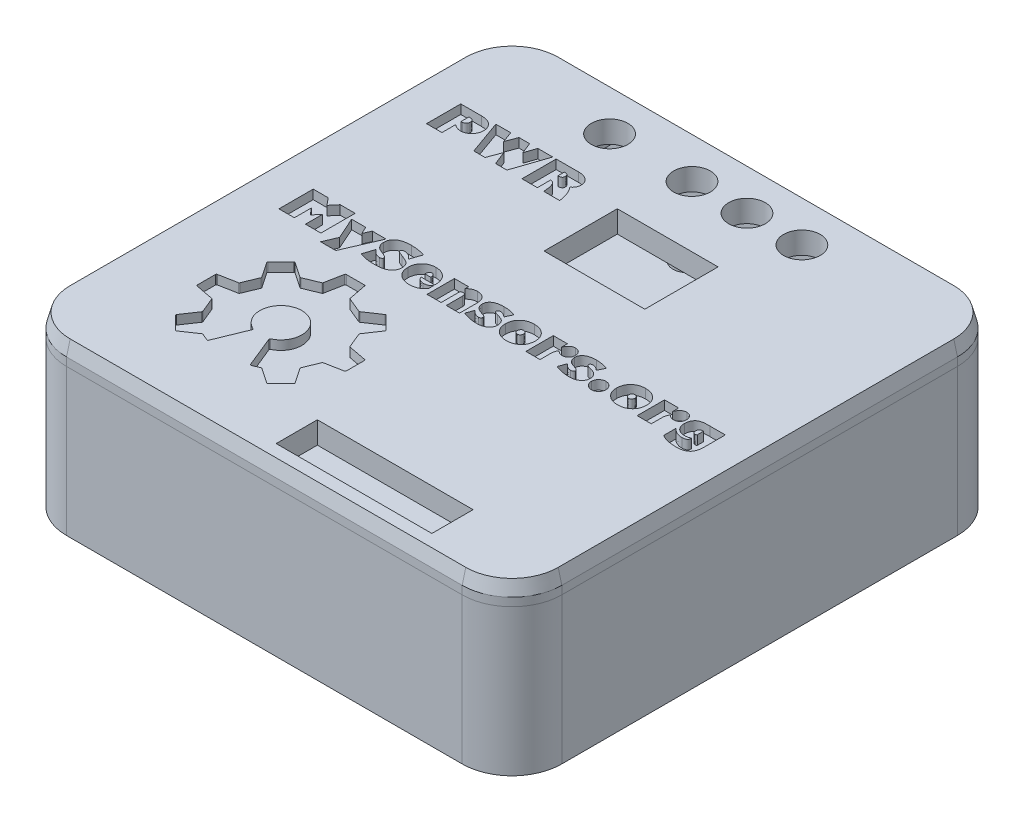
SolidWorks part; units mm, degrees
other "PCB"
other "Base"
other "Lid"
ref_plane "Front Plane" through (0, 0, 0) normal (0, 0, 1) x (1, 0, 0)
ref_plane "Top Plane" through (0, 0, 0) normal (0, 1, 0) x (1, 0, 0)
ref_plane "Right Plane" through (0, 0, 0) normal (1, 0, 0) x (0, 0, -1)
sketch "Sketch1" plane through (0, 0, 0) normal (0, 1, 0) x (1, 0, 0)
  line L1 (21.6, 25.6) -> (-21.6, 25.6)
  line L2 (25.6, 21.6) -> (25.6, -21.6)
  line L3 (21.6, -25.6) -> (-21.6, -25.6)
  line L4 (-25.6, 21.6) -> (-25.6, -21.6)
  line L5 (25.6, 25.6) -> (-25.6, -25.6) construction
  line L6 (25.6, -25.6) -> (-25.6, 25.6) construction
  line L10 (-27.04, 21.6) -> (-27.04, -21.6)
  line L11 (21.6, -27.04) -> (-21.6, -27.04)
  line L12 (27.04, 21.6) -> (27.04, -21.6)
  line L13 (21.6, 27.04) -> (-21.6, 27.04)
  circle A0 centre (-21, 21) radius 1.2
  circle A1 centre (-21, -21) radius 1.2
  circle A2 centre (21, 21) radius 1.2
  circle A3 centre (21, -21) radius 1.2
  arc A4 (-21.6, 25.6) -> (-25.6, 21.6) centre (-21.6, 21.6) ccw
  arc A5 (-21.6, -25.6) -> (-25.6, -21.6) centre (-21.6, -21.6) cw
  arc A6 (25.6, -21.6) -> (21.6, -25.6) centre (21.6, -21.6) cw
  arc A7 (21.6, 25.6) -> (25.6, 21.6) centre (21.6, 21.6) cw
  circle A8 centre (-21, 21) radius 2.2
  circle A9 centre (21, 21) radius 2.2
  circle A10 centre (21, -21) radius 1.6
  circle A11 centre (-21, -21) radius 2.2
  arc A12 (-21.6, -27.04) -> (-27.04, -21.6) centre (-21.6, -21.6) cw
  arc A13 (27.04, -21.6) -> (21.6, -27.04) centre (21.6, -21.6) cw
  arc A14 (21.6, 27.04) -> (27.04, 21.6) centre (21.6, 21.6) cw
  arc A15 (-21.6, 27.04) -> (-27.04, 21.6) centre (-21.6, 21.6) ccw
  point P0 (0, 0)
  dimension "D4" = 2.4
  dimension "D7" = 42
  dimension "D9" = 2.4
  dimension "D10" = 2.4
  dimension "D11" = 2.4
  dimension "D14" = 4
  dimension "D15" = 4
  dimension "D1" = 51.2
  dimension "D2" = 51.2
  dimension "D5" = 42
  dimension "D6" = 42
  dimension "D8" = 42
  dimension "D3" = 1
  dimension "D16" = 1.44
  dimension "D17" = 0.4
extrude "Boss-Extrude3" add sketch "Sketch1" along normal blind 13.99 contours L13 A15 L10 A12 L11 A13 L12 A14 L1 A7 L2 A6 L3 A5 L4 A4 region at (-24.9059, 0, -24.9059)
extrude "Boss-Extrude4" add sketch "Sketch1<3>" against normal blind 2 contours A7 L1 A4 L4 A5 L3 A6 L2 A11 A10 A9 A8 | L13 A15 L10 A12 L11 A13 L12 A14 L1 A7 L2 A6 L3 A5 L4 A4 | A11 A1 | A1 | A10 A3 | A3 | A8 A0 | A0 | A9 A2 | A2 region at (0.0589, 0, 0.0589) region at (-24.9059, 0, -24.9059) region at (-21, 0, -21) region at (-21, 0, 21) region at (21, 0, -21) region at (21, 0, 21) region at (-23.1378, 0, -21) region at (18.8622, 0, -21) region at (19.4453, 0, 21) region at (-23.1378, 0, 21)
sketch "Sketch1<3>" plane through (0, 0, 0) normal (0, 1, 0) x (1, 0, 0) same geometry as "Sketch1"
extrude "Boss-Extrude5" add sketch "Sketch1<4>" along normal blind 12.99 contours A3 | A1 | A2 | A0 region at (-21, 0, -21) region at (-21, 0, 21) region at (21, 0, -21) region at (21, 0, 21)
sketch "Sketch1<4>" plane through (0, 0, 0) normal (0, 1, 0) x (1, 0, 0) same geometry as "Sketch1"
extrude "Boss-Extrude6" add sketch "Sketch1<5>" along normal blind 7 contours A11 A1 | A8 A0 | A10 A3 | A9 A2 region at (-23.1378, 0, -21) region at (18.8622, 0, -21) region at (19.4453, 0, 21) region at (-23.1378, 0, 21)
sketch "Sketch1<5>" plane through (0, 0, 0) normal (0, 1, 0) x (1, 0, 0) same geometry as "Sketch1"
sketch "Sketch4" plane through (0, 7, 0) normal (0, 1, 0) x (1, 0, 0)
  line L1 (-21, 25) -> (21, 25)
  line L2 (-25, 21) -> (-25, -21)
  line L3 (-21, -25) -> (21, -25)
  line L4 (25, 21) -> (25, -21)
  line L5 (-25, 25) -> (25, -25) construction
  line L6 (-25, -25) -> (25, 25) construction
  arc A0 (-25, -21) -> (-21, -25) centre (-21, -21) ccw
  arc A1 (21, -25) -> (25, -21) centre (21, -21) ccw
  arc A2 (21, 25) -> (25, 21) centre (21, 21) cw
  arc A3 (-21, 25) -> (-25, 21) centre (-21, 21) ccw
  circle A4 centre (-21, 21) radius 1.4
  circle A5 centre (21, 21) radius 1.4
  circle A6 centre (21, -21) radius 1.4
  circle A7 centre (-21, -21) radius 1.4
  point P0 (0, 0)
  dimension "D3" = 4
  dimension "D4" = 2.8
  dimension "D5" = 2.8
  dimension "D6" = 2.8
  dimension "D7" = 2.8
  dimension "D1" = 50
  dimension "D2" = 50
  dimension "D8" = 4
  dimension "D9" = 4
  dimension "D10" = 4
  dimension "D11" = 4
extrude "Boss-Extrude7" add sketch "Sketch4" along normal blind 1.6 separate body
sketch "Sketch5" plane through (0, 8.6, 0) normal (0, 1, 0) x (1, 0, 0)
  line L0 (-21, -25) -> (21, -25) construction
  line L1 (-25, -9.2) -> (-19.2, -9.2)
  line L2 (-25, -9.2) -> (-25, -16.8)
  line L3 (-25, -16.8) -> (-19.2, -16.8)
  line L4 (-19.2, -9.2) -> (-19.2, -16.8)
  line L5 (-25, -9.2) -> (-19.2, -16.8) construction
  line L6 (-25, -16.8) -> (-19.2, -9.2) construction
  line L7 (-25, 3.8) -> (-19.2, 3.8)
  line L8 (-25, 3.8) -> (-25, -3.8)
  line L9 (-25, -3.8) -> (-19.2, -3.8)
  line L10 (-19.2, 3.8) -> (-19.2, -3.8)
  line L11 (-25, 3.8) -> (-19.2, -3.8) construction
  line L12 (-25, -3.8) -> (-19.2, 3.8) construction
  line L13 (-25, 21) -> (-25, -21) construction
  point P0 (-22.1, -13)
  point P5 (-22.1, 0)
  dimension "D4" = 7.6
  dimension "D5" = 5.8
  dimension "D6" = 5.8
  dimension "D7" = 7.6
  dimension "D8" = 12
  dimension "D9" = 25
extrude "Boss-Extrude8" add sketch "Sketch5" along normal blind 2.8
sketch "Sketch6" plane through (0, 8.6, 0) normal (0, 1, 0) x (1, 0, 0)
  line L0 (-25, 21) -> (-25, 3.8) construction
  line L1 (-21, -25) -> (21, -25) construction
  circle A0 centre (-12.0645, 22.1935) radius 1.55
  circle A1 centre (-3.0645, 22.1935) radius 1.55
  circle A2 centre (2.9355, 22.1935) radius 1.55
  circle A3 centre (8.9355, 22.1935) radius 1.55
  dimension "D1" = 3.1
  dimension "D2" = 12.9355
  dimension "D8" = 33.9355
  dimension "D3" = 47.1935
  dimension "D4" = 21.9355
  dimension "D5" = 47.1935
  dimension "D6" = 27.9355
  dimension "D7" = 47.1935
  dimension "D9" = 47.1935
extrude "Boss-Extrude9" add sketch "Sketch6" along normal blind 5
sketch "Sketch11" plane through (-27.04, 0, 0) normal (-1, 0, 0) x (0, 0, 1)
  line L0 (27.04, 13.99) -> (27.04, -2) construction
  line L4 (13, 11.4) -> (13, 8.6) construction
  line L6 (18.967, 6) -> (-8.033, 6)
  line L7 (18.967, 6) -> (18.967, 14)
  line L8 (18.967, 14) -> (-8.033, 14)
  line L9 (-8.033, 6) -> (-8.033, 14)
  line L11 (18.967, 6) -> (-8.033, 14) construction
  line L12 (0, 11.4) -> (0, 8.6) construction
  line L13 (-3.8, 10) -> (14.734, 10) construction
  line L14 (18.967, 14) -> (-8.033, 6) construction
  point P0 (0, 10)
  point P2 (5.467, 10)
  point P6 (13, 10)
  point P14 (5.467, 10)
  dimension "D1" = 27
  dimension "D2" = 8.073
  dimension "D3" = 8
extrude "Cut-Extrude1" cut sketch "Sketch11" against normal up to surface (1.44 mm away) up to face at (-25.6, 6.995, 0)
sketch "Sketch13" plane through (0, 13.99, 0) normal (0, 1, 0) x (1, 0, 0)
  line L0 (21.6, -27.04) -> (-21.6, -27.04) construction
  line L1 (27.04, 21.6) -> (27.04, -21.6) construction
  line L2 (21.6, 27.04) -> (-21.6, 27.04) construction
  line L4 (21.6, -27.04) -> (-21.6, -27.04)
  line L5 (27.04, 21.6) -> (27.04, -21.6)
  line L6 (21.6, 27.04) -> (-21.6, 27.04)
  line L7 (-27.04, -21.6) -> (-27.04, 21.6)
  arc A0 (-27.04, -21.6) -> (-21.6, -27.04) centre (-21.6, -21.6) ccw construction
  arc A1 (21.6, -27.04) -> (27.04, -21.6) centre (21.6, -21.6) ccw construction
  arc A2 (27.04, 21.6) -> (21.6, 27.04) centre (21.6, 21.6) ccw construction
  arc A3 (-21.6, 27.04) -> (-27.04, 21.6) centre (-21.6, 21.6) ccw construction
  arc A4 (-27.04, -21.6) -> (-21.6, -27.04) centre (-21.6, -21.6) ccw
  arc A5 (21.6, -27.04) -> (27.04, -21.6) centre (21.6, -21.6) ccw
  arc A6 (27.04, 21.6) -> (21.6, 27.04) centre (21.6, 21.6) ccw
  arc A7 (-21.6, 27.04) -> (-27.04, 21.6) centre (-21.6, 21.6) ccw
  circle A16 centre (-11.54, 22.1935) radius 2
  circle A17 centre (-2.54, 22.1935) radius 2
  circle A18 centre (3.46, 22.1935) radius 2
  circle A19 centre (9.46, 22.1935) radius 2
  dimension "D1" = 4
  dimension "D2" = 4
  dimension "D3" = 4
  dimension "D4" = 4
  dimension "D5" = 15.5
  dimension "D6" = 9
  dimension "D7" = 6
  dimension "D8" = 6
extrude "Boss-Extrude11" add sketch "Sketch13" along normal blind 2.4 separate body
chamfer "Chamfer1" distance 1.5 distance2 0.4 8 edges at (25.4467, 16.39, 25.4467) (27.04, 16.39, 0) (0, 16.39, 27.04) (25.4467, 16.39, -25.4467) (-25.4467, 16.39, 25.4467) (0, 16.39, -27.04) (-27.04, 16.39, 0) (-25.4467, 16.39, -25.4467) first distance on face at (24.8833, 15.19, 24.8833) first distance on face at (27.04, 15.19, 0) first distance on face at (0, 15.19, 27.04) first distance on face at (24.8833, 15.19, -24.8833) first distance on face at (-24.8833, 15.19, 24.8833) first distance on face at (0, 15.19, -27.04) first distance on face at (-27.04, 15.19, 0) first distance on face at (-24.8833, 15.19, -24.8833)
sketch "Sketch16" plane through (0, 13.99, 0) normal (0, -1, 0) x (1, 0, 0)
  circle A0 centre (21, 21) radius 1.4 construction
  circle A1 centre (21, 21) radius 1.4
  circle A2 centre (-21, 21) radius 1.4 construction
  circle A3 centre (-21, 21) radius 1.4
  circle A4 centre (21, -21) radius 1.4 construction
  circle A5 centre (21, -21) radius 1.4
  circle A6 centre (-21, -21) radius 1.4 construction
  circle A7 centre (-21, -21) radius 1.4
  circle A8 centre (-21, -21) radius 2.2 construction
  circle A9 centre (21, -21) radius 2.2 construction
  circle A11 centre (-21, 21) radius 2.2 construction
  circle A12 centre (-21, -21) radius 2.2
  circle A13 centre (21, -21) radius 2.2
  circle A14 centre (21, 21) radius 2.38
  circle A15 centre (-21, 21) radius 2.2
  dimension "D1" = 0.98
extrude "Boss-Extrude14" add sketch "Sketch16" along normal blind 2
sketch "Sketch17" plane through (0, 13.99, 0) normal (0, -1, 0) x (1, 0, 0)
  line L0 (-21.6, 23.6) -> (21.6, 23.6)
  line L1 (23.6, -21.6) -> (23.6, 21.6)
  line L2 (-21.6, 25.6) -> (21.6, 25.6)
  line L3 (-21.6, 25.6) -> (21.6, 25.6)
  line L4 (-21.6, -23.6) -> (-14.8497, -23.6)
  line L5 (-23.6, 21.6) -> (-23.6, 18.967)
  line L6 (-23.6, 18.967) -> (-24.1, 18.967)
  line L7 (-23.6, -21.6) -> (-25.6, -21.6)
  line L8 (12.271, -23.6) -> (12.271, -25.6)
  line L9 (-14.8497, -23.6) -> (-14.8497, -25.6)
  line L10 (12.271, -23.6) -> (21.6, -23.6)
  line L11 (12.271, -25.6) -> (21.6, -25.6)
  line L12 (-21.6, -23.6) -> (21.6, -23.6) construction
  line L14 (-21.6, -25.6) -> (21.6, -25.6) construction
  line L18 (-25.6, 21.6) -> (-25.6, -21.6)
  line L19 (-21.6, -25.6) -> (21.6, -25.6)
  line L20 (25.6, -21.6) -> (25.6, 21.6)
  line L21 (-25.6, 21.6) -> (-25.6, 18.967)
  line L22 (-21.6, -25.6) -> (-14.8497, -25.6)
  line L23 (25.6, -21.6) -> (25.6, 21.6)
  line L26 (-25.6, 18.967) -> (-24.1, 18.967)
  arc A0 (-21.6, 23.6) -> (-23.6, 21.6) centre (-21.6, 21.6) ccw
  arc A1 (23.6, 21.6) -> (21.6, 23.6) centre (21.6, 21.6) ccw
  arc A2 (21.6, -23.6) -> (23.6, -21.6) centre (21.6, -21.6) ccw
  arc A3 (-23.6, -21.6) -> (-21.6, -23.6) centre (-21.6, -21.6) ccw
  arc A20 (-21.6, 25.6) -> (-25.6, 21.6) centre (-21.6, 21.6) ccw
  arc A21 (-25.6, -21.6) -> (-21.6, -25.6) centre (-21.6, -21.6) ccw
  arc A22 (21.6, -25.6) -> (25.6, -21.6) centre (21.6, -21.6) ccw
  arc A23 (25.6, 21.6) -> (21.6, 25.6) centre (21.6, 21.6) ccw
  arc A24 (-21.6, 25.6) -> (-25.6, 21.6) centre (-21.6, 21.6) ccw
  arc A25 (-25.6, -21.6) -> (-21.6, -25.6) centre (-21.6, -21.6) ccw
  arc A26 (21.6, -25.6) -> (25.6, -21.6) centre (21.6, -21.6) ccw
  arc A27 (25.6, 21.6) -> (21.6, 25.6) centre (21.6, 21.6) ccw
  point P11 (-24.1, -21.1)
  point P12 (-24.1, 21.1)
  dimension "D1" = 1.44
  dimension "D2" = 1.44
  dimension "D4" = 2
extrude "Boss-Extrude15" add sketch "Sketch17" along normal blind 2
chamfer "Chamfer2" distance 1 distance2 0.2 7 edges at (24.4284, 11.99, -24.4284) (25.6, 11.99, 0) (24.4284, 11.99, 24.4284) (0, 11.99, 25.6) (-24.4284, 11.99, 24.4284) (-25.6, 11.99, 20.2835) (16.9355, 11.99, -25.6) first distance on face at (24.0142, 12.99, -24.0142) first distance on face at (25.6, 12.99, 0) first distance on face at (24.0142, 12.99, 24.0142) first distance on face at (0, 12.99, 25.6) first distance on face at (-24.0142, 12.99, 24.0142) first distance on face at (-25.6, 12.99, 20.2835) first distance on face at (16.9355, 12.99, -25.6)
chamfer "Chamfer3" distance 0.2 distance2 0.5 3 edges at (21, 11.99, -22.4) (-21, 11.99, -22.4) (-21, 11.99, 19.6) first distance on face at (21, 11.99, -23.2) first distance on face at (-21, 11.99, -23.2) first distance on face at (-21, 11.99, 18.8)
sketch "Sketch19" plane through (0, 16.39, 0) normal (0, 1, 0) x (1, 0, 0)
  line L118 (-12.5358, -15.8285) -> (-13.9134, -19.2023)
  line L119 (-14.0508, -19.2596) -> (-14.799, -18.9497)
  line L120 (-14.898, -18.9597) -> (-16.5435, -20.073)
  line L121 (-16.6766, -20.0603) -> (-18.0826, -18.6543)
  line L122 (-18.0953, -18.5213) -> (-16.982, -16.8757)
  line L123 (-16.972, -16.7767) -> (-17.6488, -15.1427)
  line L124 (-17.7259, -15.0798) -> (-19.6767, -14.7034)
  line L125 (-19.7618, -14.6003) -> (-19.7618, -12.612)
  line L126 (-19.6767, -12.5089) -> (-17.7259, -12.1326)
  line L127 (-17.6488, -12.0697) -> (-16.972, -10.4356)
  line L128 (-16.982, -10.3366) -> (-18.0953, -8.6911)
  line L129 (-18.0826, -8.558) -> (-16.6766, -7.1521)
  line L130 (-16.5435, -7.1393) -> (-14.898, -8.2526)
  line L131 (-14.799, -8.2627) -> (-13.165, -7.5858)
  line L132 (-13.1021, -7.5087) -> (-12.7257, -5.5579)
  line L133 (-12.6226, -5.4728) -> (-10.6343, -5.4728)
  line L134 (-10.5312, -5.5579) -> (-10.1549, -7.5087)
  line L135 (-10.0919, -7.5858) -> (-8.4579, -8.2627)
  line L136 (-8.3589, -8.2526) -> (-6.7134, -7.1393)
  line L137 (-6.5803, -7.1521) -> (-5.1744, -8.558)
  line L138 (-5.1616, -8.6911) -> (-6.2749, -10.3366)
  line L139 (-6.285, -10.4356) -> (-5.6081, -12.0697)
  line L140 (-5.531, -12.1326) -> (-3.5802, -12.5089)
  line L141 (-3.4951, -12.612) -> (-3.4951, -14.6003)
  line L142 (-3.5802, -14.7034) -> (-5.531, -15.0798)
  line L143 (-5.6081, -15.1427) -> (-6.285, -16.7767)
  line L144 (-6.2749, -16.8757) -> (-5.1616, -18.5213)
  line L145 (-5.1744, -18.6543) -> (-6.5803, -20.0603)
  line L146 (-6.7134, -20.073) -> (-8.3589, -18.9597)
  line L147 (-8.4579, -18.9497) -> (-9.2062, -19.2596)
  line L148 (-9.3435, -19.2023) -> (-10.7211, -15.8285)
  arc A468 (-10.6678, -15.6934) -> (-12.5892, -15.6934) centre (-11.6285, -13.6062) ccw
  arc A469 (-12.5358, -15.8285) -> (-12.5892, -15.6934) centre (-12.6331, -15.7888) ccw
  arc A470 (-14.0508, -19.2596) -> (-13.9134, -19.2023) centre (-14.0106, -19.1626) ccw
  arc A471 (-14.799, -18.9497) -> (-14.898, -18.9597) centre (-14.8392, -19.0467) ccw
  arc A472 (-16.6766, -20.0603) -> (-16.5435, -20.073) centre (-16.6024, -19.986) ccw
  arc A473 (-18.0953, -18.5213) -> (-18.0826, -18.6543) centre (-18.0083, -18.5801) ccw
  arc A474 (-16.982, -16.8757) -> (-16.972, -16.7767) centre (-17.069, -16.8169) ccw
  arc A475 (-17.6488, -15.1427) -> (-17.7259, -15.0798) centre (-17.7458, -15.1829) ccw
  arc A476 (-19.7618, -14.6003) -> (-19.6767, -14.7034) centre (-19.6568, -14.6003) ccw
  arc A477 (-19.6767, -12.5089) -> (-19.7618, -12.612) centre (-19.6568, -12.612) ccw
  arc A478 (-17.7259, -12.1326) -> (-17.6488, -12.0697) centre (-17.7458, -12.0295) ccw
  arc A479 (-16.972, -10.4356) -> (-16.982, -10.3366) centre (-17.069, -10.3955) ccw
  arc A480 (-18.0826, -8.558) -> (-18.0953, -8.6911) centre (-18.0083, -8.6322) ccw
  arc A481 (-16.5435, -7.1393) -> (-16.6766, -7.1521) centre (-16.6024, -7.2263) ccw
  arc A482 (-14.898, -8.2526) -> (-14.799, -8.2627) centre (-14.8392, -8.1657) ccw
  arc A483 (-13.165, -7.5858) -> (-13.1021, -7.5087) centre (-13.2052, -7.4888) ccw
  arc A484 (-12.6226, -5.4728) -> (-12.7257, -5.5579) centre (-12.6226, -5.5778) ccw
  arc A485 (-10.5312, -5.5579) -> (-10.6343, -5.4728) centre (-10.6343, -5.5778) ccw
  arc A486 (-10.1549, -7.5087) -> (-10.0919, -7.5858) centre (-10.0518, -7.4888) ccw
  arc A487 (-8.4579, -8.2627) -> (-8.3589, -8.2526) centre (-8.4177, -8.1657) ccw
  arc A488 (-6.5803, -7.1521) -> (-6.7134, -7.1393) centre (-6.6545, -7.2263) ccw
  arc A489 (-5.1616, -8.6911) -> (-5.1744, -8.558) centre (-5.2486, -8.6322) ccw
  arc A490 (-6.2749, -10.3366) -> (-6.285, -10.4356) centre (-6.188, -10.3955) ccw
  arc A491 (-5.6081, -12.0697) -> (-5.531, -12.1326) centre (-5.5111, -12.0295) ccw
  arc A492 (-3.4951, -12.612) -> (-3.5802, -12.5089) centre (-3.6001, -12.612) ccw
  arc A493 (-3.5802, -14.7034) -> (-3.4951, -14.6003) centre (-3.6001, -14.6003) ccw
  arc A494 (-5.531, -15.0798) -> (-5.6081, -15.1427) centre (-5.5111, -15.1829) ccw
  arc A495 (-6.285, -16.7767) -> (-6.2749, -16.8757) centre (-6.188, -16.8169) ccw
  arc A496 (-5.1744, -18.6543) -> (-5.1616, -18.5213) centre (-5.2486, -18.5801) ccw
  arc A497 (-6.7134, -20.073) -> (-6.5803, -20.0603) centre (-6.6545, -19.986) ccw
  arc A498 (-8.3589, -18.9597) -> (-8.4579, -18.9497) centre (-8.4177, -19.0467) ccw
  arc A499 (-9.3435, -19.2023) -> (-9.2062, -19.2596) centre (-9.2463, -19.1626) ccw
  arc A500 (-10.6678, -15.6934) -> (-10.7211, -15.8285) centre (-10.6239, -15.7888) ccw
extrude "Cut-Extrude3" cut sketch "Sketch19" against normal blind 1
sketch "Sketch20" plane through (0, 16.39, 0) normal (0, 1, 0) x (1, 0, 0)
  line L0 (-21.6, 27.04) -> (21.6, 27.04) construction
  line L1 (-4.04, 15.54) -> (6.96, 15.54)
  line L2 (-4.04, 15.54) -> (-4.04, 7.54)
  line L3 (-4.04, 7.54) -> (6.96, 7.54)
  line L4 (6.96, 15.54) -> (6.96, 7.54)
  line L5 (-4.04, 15.54) -> (6.96, 7.54) construction
  line L6 (-4.04, 7.54) -> (6.96, 15.54) construction
  line L7 (-0.46, -20.79) -> (16.54, -20.79)
  line L8 (-0.46, -20.79) -> (-0.46, -25.29)
  line L9 (-0.46, -25.29) -> (16.54, -25.29)
  line L10 (16.54, -20.79) -> (16.54, -25.29)
  line L11 (-0.46, -20.79) -> (16.54, -25.29) construction
  line L12 (-0.46, -25.29) -> (16.54, -20.79) construction
  line L13 (-27.04, 21.6) -> (-27.04, 8.033) construction
  line L15 (27.04, 21.6) -> (27.04, -21.6) construction
  line L16 (21.6, -27.04) -> (-21.6, -27.04) construction
  point P0 (1.46, 11.54)
  point P5 (8.04, -23.04)
  point P14 (8.04, -20.79)
  point P16 (-0.46, -23.04)
  dimension "D1" = 19.5
  dimension "D2" = 8
  dimension "D3" = 11
  dimension "D4" = 34
  dimension "D5" = 4.5
  dimension "D6" = 17
  dimension "D7" = 19
  dimension "D8" = 4
extrude "Cut-Extrude4" cut sketch "Sketch20" against normal up to surface (4.4 mm away) up to face at (4.309, 11.99, 5.146)
sketch "Sketch21" plane through (0, 16.39, 0) normal (0, 1, 0) x (1, 0, 0)
  text T1 "PWR\r\n\r\nMySensors.org" font "Gill Sans Ultra Bold" height in points 14
  point P1 (-21.1473, 14.4173)
  point P3 (-11.4063, 0.4683)
  point P4 (-20.5872, 0.9857)
  point P5 (-21.1473, 0.8489)
  point P6 (-23.3881, 0.8569)
extrude "Cut-Extrude5" cut sketch "Sketch21" against normal blind 1
